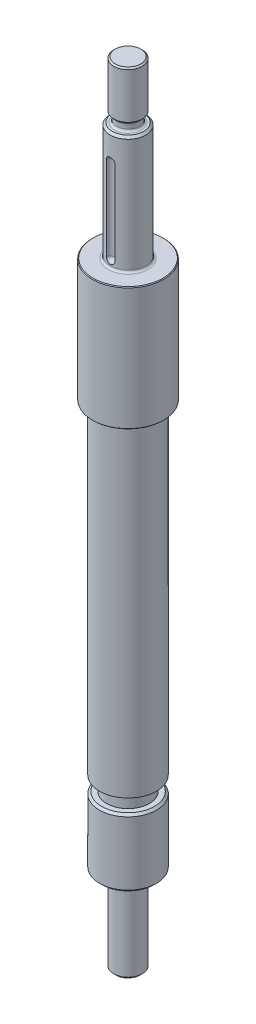
SolidWorks part; units mm, degrees
ref_plane "Front Plane" through (0, 0, 0) normal (0, 0, 1) x (1, 0, 0)
ref_plane "Top Plane" through (0, 0, 0) normal (0, 1, 0) x (1, 0, 0)
ref_plane "Right Plane" through (0, 0, 0) normal (1, 0, 0) x (0, 0, -1)
sketch "Sketch1" plane through (0, 0, 0) normal (0, 0, 1) x (1, 0, 0)
  line L0 (0, 0) -> (0, 119.1505) construction
  line L1 (0, 0) -> (2, 0)
  line L2 (2, 0) -> (2, 12)
  line L3 (2, 12) -> (4, 12)
  line L4 (4, 12) -> (4, 21.5)
  line L5 (4, 69) -> (5, 69)
  line L7 (5, 86.3) -> (2.5, 86.3)
  line L8 (2.5, 86.3) -> (2.5, 102.8)
  line L9 (2, 110.8) -> (0, 110.8)
  line L10 (2, 110.8) -> (2, 104)
  line L11 (1.6, 102.8) -> (2.5, 102.8)
  line L12 (0, 110.8) -> (0, 0)
  line L13 (5, 86.3) -> (5, 69)
  line L15 (2, 104) -> (1.6, 104)
  line L16 (1.6, 104) -> (1.6, 102.8)
  line L17 (4, 23.5) -> (4, 69)
  line L18 (4, 21.5) -> (3, 21.5)
  line L20 (4, 23.5) -> (3, 23.5)
  line L21 (3, 21.5) -> (3, 23.5)
  line L22 (0, 0) -> (0, -13.7807) construction
  dimension "D1" = 17.3
  dimension "D2" = 8
  dimension "D3" = 5
  dimension "D4" = 4
  dimension "D5" = 3.2
  dimension "D6" = 16.5
  dimension "D7" = 10
  dimension "D8" = 1.2
  dimension "D9" = 8
  dimension "D10" = 45.5
  dimension "D11" = 12
  dimension "D12" = 6
  dimension "D13" = 2
  dimension "D14" = 11.5
revolve "Revolve1" add sketch "Sketch1" angle 360 about L0
ref_plane "Plane2" through (0, 86.8, 0) normal (0, 1, 0) x (1, 0, 0)
sketch "Sketch2" plane through (0, 86.8, 0) normal (0, 1, 0) x (1, 0, 0)
  line L0 (0, 0) -> (6.8447, 0) construction
  circle A0 centre (0, 2.5) radius 0.6
  circle A1 centre (0, 0) radius 2.5 construction
  circle A2 centre (0, 0) radius 2.5 construction
  circle A3 centre (0, -2.5) radius 0.6
  dimension "D1" = 1.2
extrude "Cut-Extrude1" cut sketch "Sketch2" along normal offset from surface (13 mm away) 3 up to face at (0, 102.8, -1.6)
fillet "Fillet1" radius 0.6 4 edges at (0, 99.8, -1.9) (0, 86.8, -1.9) (0, 86.8, 1.9) (0, 99.8, 1.9)
chamfer "Chamfer1" distance 0.1 angle 45 2 edges at (0, 69, -5) (0, 86.3, -5)
chamfer "Chamfer2" distance 0.3 angle 45 2 edges at (0, 21.5, -4) (0, 12, -4)
chamfer "Chamfer3" distance 0.3 angle 45 1 edges at (0, 0, -2)
chamfer "Chamfer4" distance 0.3 angle 45 1 edges at (0, 102.8, -2.5)
chamfer "Chamfer5" distance 0.2 angle 45 2 edges at (0, 104, -2) (0, 110.8, -2)
fillet "Fillet2" radius 0.3 6 edges at (0, 23.5, -3) (0, 12, -2) (0, 69, -4) (0, 86.3, -2.5) (0, 104, -1.6) (0, 102.8, -1.6)
